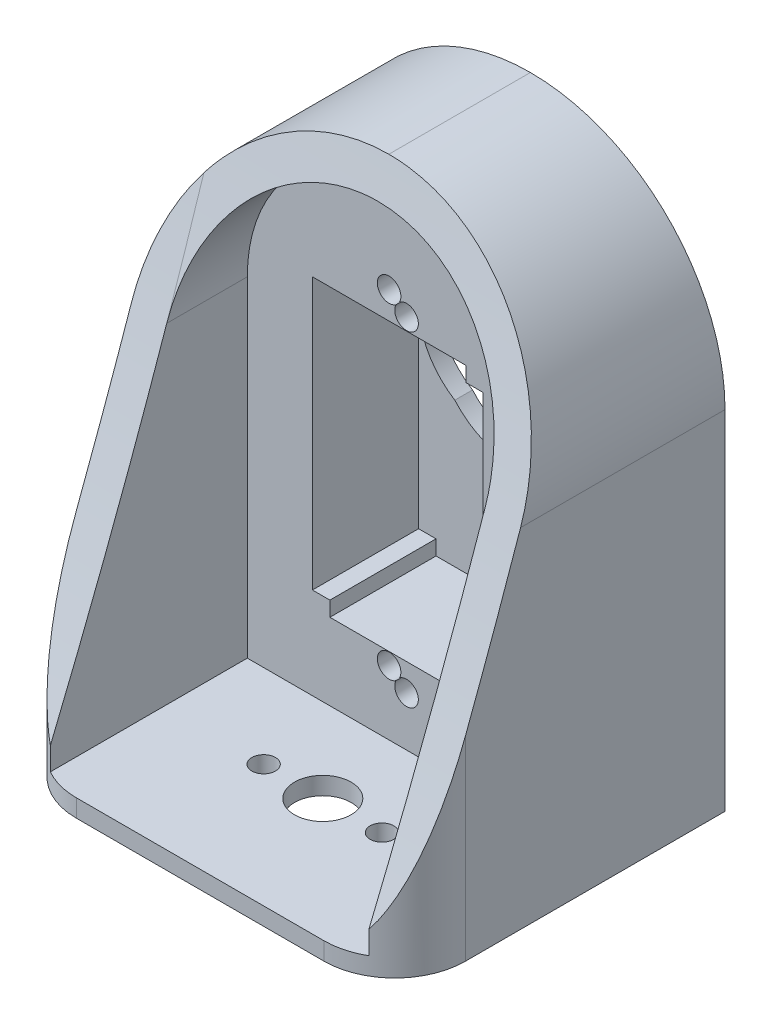
SolidWorks part; units mm, degrees
ref_plane "Front Plane" through (0, 0, 0) normal (0, 0, 1) x (1, 0, 0)
ref_plane "Top Plane" through (0, 0, 0) normal (0, 1, 0) x (1, 0, 0)
ref_plane "Right Plane" through (0, 0, 0) normal (1, 0, 0) x (0, 0, -1)
sketch "Sketch1" plane through (0, 0, 0) normal (0, 1, 0) x (1, 0, 0)
  line L1 (-16.5, -14) -> (16.5, -14)
  line L2 (-16.5, -14) -> (-16.5, 14)
  line L3 (-16.5, 14) -> (16.5, 14)
  line L4 (16.5, -14) -> (16.5, 14)
  line L5 (-16.5, -14) -> (16.5, 14) construction
  line L6 (-16.5, 14) -> (16.5, -14) construction
  point P0 (0, 0)
  dimension "D1" = 33
  dimension "D2" = 28
extrude "Boss-Extrude1" add sketch "Sketch1" along normal blind 46
sketch "Sketch3" plane through (16.5, 0, 0) normal (1, 0, 0) x (0, 0, -1)
  line L2 (-14, 0) -> (14, 0) construction
  line L3 (14, 46) -> (11.5, 46)
  line L4 (14, 46) -> (14, 21)
  line L5 (14, 21) -> (11.5, 21)
  line L6 (11.5, 46) -> (11.5, 21)
  line L7 (-14, 46) -> (3.5, 46)
  line L8 (-14, 46) -> (-14, 1.5)
  line L9 (-14, 1.5) -> (3.5, 1.5)
  line L10 (3.5, 46) -> (3.5, 1.5)
  line M11 (14, 46) -> (-14, 46)
  line M12 (-14, 46) -> (-14, 0)
  dimension "D1" = 1.5
  dimension "D2" = 8
  dimension "D3" = 2.5
  dimension "D4" = 25
extrude "Cut-Extrude2" cut sketch "Sketch3" against normal through all contours L10 L9 M11 M12 region at (16.5, 23.75, 5.25)
sketch "Sketch5" plane through (16.5, 0, 0) normal (1, 0, 0) x (0, 0, -1)
  line L0 (3.5, 46) -> (2, 46)
  line L1 (3.5, 46) -> (3.5, 1.5)
  line L2 (3.5, 1.5) -> (-14, 1.5)
  spline S0 degree 2 poles (2, 46) (-4.8571, 23.3254) (-14, 1.5) knots 0 0 0 1 1 1
  dimension "D1" = 1.5
extrude "Boss-Extrude2" add sketch "Sketch5" against normal blind 3
sketch "Sketch6" plane through (-16.5, 0, 0) normal (-1, 0, 0) x (0, 0, 1)
  line L3 (-2, 46) -> (-3.5, 46)
  line L4 (-3.5, 46) -> (-3.5, 1.5)
  line L5 (-3.5, 1.5) -> (14, 1.5)
  line L6 (-2, 46) -> (-3.5, 46)
  line L7 (-3.5, 46) -> (-3.5, 1.5)
  line L8 (-3.5, 1.5) -> (14, 1.5)
  parabola Q1 (14, 1.5) -> (-2, 46) focus (221.9743, 98.8362) apex (7.0828, 19.0115)
  parabola Q2 (14, 1.5) -> (-2, 46) focus (221.9743, 98.8362) apex (7.0828, 19.0115)
  dimension "D1" = 0
extrude "Boss-Extrude3" add sketch "Sketch6" against normal blind 3
sketch "Sketch8" plane through (13.5, 0, 0) normal (-1, 0, 0) x (0, 0, 1)
  line L0 (-3.5, 43) -> (-1.0816, 43)
  line L1 (-3.5, 1.5) -> (-3.5, 46) construction
  line L2 (-3.5, 46) -> (-2, 46) construction
  line L6 (-2, 46) -> (-3.5, 46)
  line L7 (-3.5, 46) -> (-3.5, 1.5)
  line L8 (-3.5, 1.5) -> (14, 1.5)
  line L9 (-2, 46) -> (-3.5, 46)
  line L10 (-3.5, 46) -> (-3.5, 1.5)
  line L11 (-3.5, 1.5) -> (14, 1.5)
  parabola Q0 (-2, 46) -> (14, 1.5) focus (221.9743, 98.8362) apex (7.0828, 19.0115) construction
  parabola Q2 (14, 1.5) -> (-2, 46) focus (221.9743, 98.8362) apex (7.0828, 19.0115)
  parabola Q3 (14, 1.5) -> (-2, 46) focus (221.9743, 98.8362) apex (7.0828, 19.0115)
  spline M2 degree 2 poles (-2, 46) (4.8571, 23.3254) (14, 1.5) knots 0 0 0 1 1 1
  line M3 (-2, 46) -> (-3.5, 46)
  line M4 (-3.5, 46) -> (-3.5, 1.5)
  dimension "D1" = 3
  dimension "D2" = 0
extrude "Boss-Extrude4" add sketch "Sketch8" along normal up to surface (27 mm away) contours L0 M4 M2 M3 region at (13.5, 44.3827, -2.5034) up to face at (-13.5, 18.1875, 1.0625)
fillet "Fillet2" radius 13.5 2 edges
fillet "Fillet3" radius 16.5 2 edges at (-16.5, 46, -8) (16.5, 46, -8)
sketch "Sketch9" plane through (0, 0, -3.5) normal (0, 0, 1) x (1, 0, 0)
  line L0 (-13.5, 1.5) -> (13.5, 1.5) construction
  line L1 (-6.5, 8) -> (6.5, 8)
  line L2 (-6.5, 8) -> (-6.5, 31)
  line L3 (-6.5, 31) -> (6.5, 31)
  line L4 (6.5, 8) -> (6.5, 31)
  line L5 (-6.5, 8) -> (6.5, 31) construction
  line L6 (-6.5, 31) -> (6.5, 8) construction
  point P0 (0, 19.5)
  dimension "D1" = 13
  dimension "D2" = 23
  dimension "D3" = 6.5
sketch "Sketch13" plane through (-1.4801, -2.2378, -3.5) normal (0, 0, 1) x (1, 0, 0)
  line L1 (-6.5, 11.5) -> (6.5, 11.5)
  line L2 (-6.5, 11.5) -> (-6.5, 34.5)
  line L3 (-6.5, 34.5) -> (6.5, 34.5)
  line L4 (6.5, 11.5) -> (6.5, 34.5)
  line L5 (-6.5, 11.5) -> (6.5, 34.5) construction
  line L6 (-6.5, 34.5) -> (6.5, 11.5) construction
  point P0 (0, 23)
  dimension "D1" = 13
  dimension "D2" = 23
extrude "Cut-Extrude7" cut sketch "Sketch13" against normal blind 9
sketch "Sketch15" plane through (-1.4801, -2.2378, -12.5) normal (0, 0, 1) x (1, 0, 0)
  line L1 (6.5, 34.5) -> (-6.5, 34.5) construction
  circle A0 centre (0, 28) radius 6.5
  dimension "D1" = 13
  dimension "D2" = 6.5
extrude "Cut-Extrude8" cut sketch "Sketch15" against normal through all
sketch "Sketch17" plane through (-1.4801, -2.2378, -3.5) normal (0, 0, 1) x (1, 0, 0)
  line L1 (6.5, 34.5) -> (0, 34.5) construction
  circle A0 centre (0, 36.8) radius 1
  circle A1 centre (0, 9.2) radius 1
  dimension "D1" = 27.6
  dimension "D2" = 2
  dimension "D3" = 2
  dimension "D4" = 2.3
extrude "Cut-Extrude9" cut sketch "Sketch17" against normal blind 8
sketch "Sketch18" plane through (0, 1.5, 0) normal (0, 1, 0) x (1, 0, 0)
  line L0 (0, 2) -> (0, 14) construction
  circle A0 centre (0, -3.5999) radius 2.4
  circle A1 centre (5.0159, -3.5999) radius 1
  circle A2 centre (-5.0159, -3.5999) radius 1
extrude "Cut-Extrude10" cut sketch "Sketch18" against normal through all
extrude "Cut-Extrude4" cut sketch "Sketch9" against normal blind 9
sketch "Sketch10" plane through (0, 0, -12.5) normal (0, 0, 1) x (1, 0, 0)
  line L1 (6.5, 31) -> (5.0199, 31) construction
  circle A0 centre (0, 24.5) radius 6.5
  dimension "D1" = 13
  dimension "D2" = 6.5
extrude "Cut-Extrude5" cut sketch "Sketch10" against normal through all
sketch "Sketch11" plane through (0, 0, -3.5) normal (0, 0, 1) x (1, 0, 0)
  line L1 (6.5, 31) -> (5.0199, 31) construction
  circle A0 centre (0, 33.3) radius 1
  circle A1 centre (0, 5.7) radius 1
  dimension "D1" = 27.6
  dimension "D2" = 2
  dimension "D3" = 2
  dimension "D4" = 2.3
extrude "Cut-Extrude6" cut sketch "Sketch11" against normal blind 8
fillet "Fillet4" radius 6 2 edges at (-16.5, 0.75, 14) (16.5, 0.75, 14)
